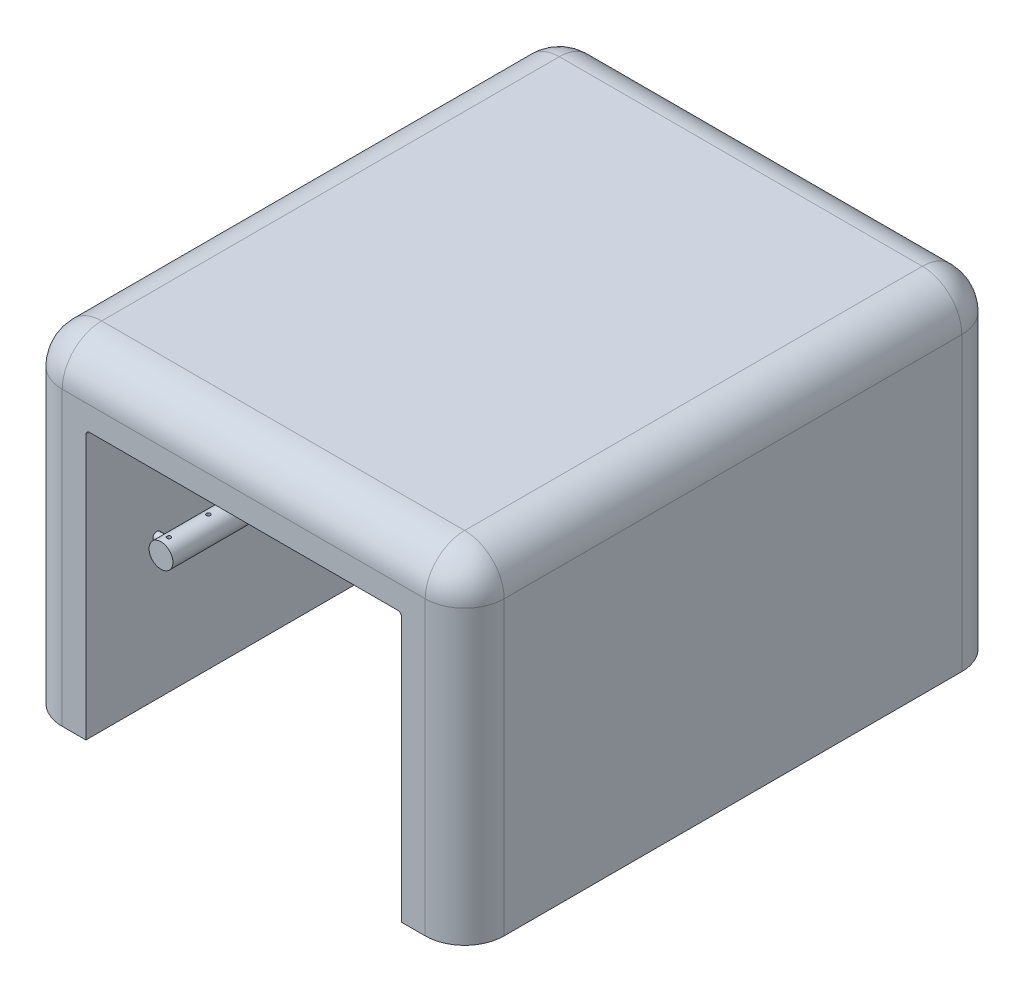
SolidWorks part; units mm, degrees
ref_plane "Front Plane" through (0, 0, 0) normal (0, 0, 1) x (1, 0, 0)
ref_plane "Top Plane" through (0, 0, 0) normal (0, 1, 0) x (1, 0, 0)
ref_plane "Right Plane" through (0, 0, 0) normal (1, 0, 0) x (0, 0, -1)
sketch "Sketch1" plane through (0, 0, 0) normal (1, 0, 0) x (0, 0, -1)
  line L1 (0, 0) -> (680, 0)
  line L2 (0, 0) -> (0, 420)
  line L3 (0, 420) -> (680, 420)
  line L4 (680, 0) -> (680, 420)
  dimension "D1" = 420
  dimension "D2" = 680
extrude "Boss-Extrude1" add sketch "Sketch1" along normal blind 560
sketch "Sketch4" plane through (0, 0, 0) normal (0, 0, 1) x (1, 0, 0)
  line L0 (560, 0) -> (0, 0) construction
  line L1 (80, 0) -> (480, 0)
  line L2 (80, 0) -> (80, 340)
  line L3 (80, 340) -> (480, 340)
  line L4 (480, 0) -> (480, 340)
  line L5 (560, 420) -> (560, 0) construction
  line L6 (560, 420) -> (0, 420) construction
  line L7 (0, 420) -> (0, 0) construction
  dimension "D1" = 80
  dimension "D2" = 80
  dimension "D3" = 80
extrude "Cut-Extrude1" cut sketch "Sketch4" against normal offset from surface (560 mm away) 120 up to face at (280, 210, -680)
ref_plane "Plane1" through (80, 0, 0) normal (1, 0, 0) x (0, 0, -1)
sketch "Sketch6" plane through (80, 0, 0) normal (1, 0, 0) x (0, 0, -1)
  line L1 (580, 80) -> (560, 80)
  line L2 (560, 80) -> (560, 160)
  line L3 (680, 0) -> (680, 420) construction
  line L4 (0, 0) -> (680, 0) construction
  line L5 (560, 160) -> (580, 160)
  line L6 (580, 160) -> (580, 80)
  dimension "D1" = 80
  dimension "D2" = 120
  dimension "D3" = 100
  dimension "D4" = 80
extrude "Cut-Extrude2" cut sketch "Sketch6" along normal up to surface (400 mm away) up to face at (480, 170, -280)
sketch "Sketch7" plane through (0, 0, -560) normal (0, 0, 1) x (1, 0, 0)
  line L3 (80, 160) -> (80, 340) construction
  line L5 (480, 160) -> (80, 160) construction
  circle A0 centre (105.125, 180.125) radius 15.125
  point P7 (280, 340)
  dimension "D1" = 30.25
  dimension "D2" = 5
  dimension "D3" = 10
extrude "Boss-Extrude2" add sketch "Sketch7" along normal offset from surface (490 mm away) 70 up to face at (280, 190, 0)
ref_plane "Plane2" through (0, 195.25, 0) normal (0, 1, 0) x (1, 0, 0)
ref_plane "Plane3" through (0, 0, -74) normal (0, 0, 1) x (1, 0, 0)
sketch "Sketch10" plane through (0, 0, -70) normal (0, 0, 1) x (1, 0, 0)
  circle A0 centre (105.125, 180.125) radius 11.125
  circle A1 centre (105.125, 180.125) radius 15.125 construction
  dimension "D1" = 4
extrude "Cut-Extrude3" cut sketch "Sketch10" against normal up to surface (490 mm away) from surface up to face at (120.25, 180.125, -560) starting at plane "Plane3"
sketch "Sketch9" plane through (0, 195.25, 0) normal (0, 1, 0) x (1, 0, 0)
  line L0 (90, 530) -> (120.25, 530) construction
  line L1 (90, 560) -> (90, 70) construction
  line L2 (120.25, 70) -> (120.25, 560) construction
  line L3 (80, 560) -> (480, 560) construction
  circle A0 centre (105.125, 530) radius 2.5
  circle A1 centre (105.125, 480) radius 2.5
  circle A2 centre (105.125, 430) radius 2.5
  circle A3 centre (105.125, 380) radius 2.5
  circle A4 centre (105.125, 330) radius 2.5
  circle A5 centre (105.125, 280) radius 2.5
  circle A6 centre (105.125, 230) radius 2.5
  circle A7 centre (105.125, 180) radius 2.5
  circle A8 centre (105.125, 130) radius 2.5
  circle A9 centre (105.125, 80) radius 2.5
  point P10 (105.125, 530)
  dimension "D1" = 5
  dimension "D2" = 30
  dimension "D3" = 10
extrude "Cut-Extrude4" cut sketch "Sketch9" against normal up to next
ref_axis "Axis1" through (280, 340, -560) along (0, -1, 0)
ref_plane "Plane4" through (280, 0, 0) normal (1, 0, 0) x (0, 0, -1)
sketch "Sketch11" plane through (80, 0, 0) normal (1, 0, 0) x (0, 0, -1)
  line L0 (70, 195.25) -> (70, 165) construction
  circle A0 centre (90, 179) radius 5
  dimension "D2" = 10
  dimension "D1" = 20
  dimension "D3" = 19
extrude "Boss-Extrude3" add sketch "Sketch11" along normal up to next
mirror "Mirror1" about plane through (280, 0, 0) normal (1, 0, 0) of "Boss-Extrude3", "Cut-Extrude3", "Cut-Extrude4", "Boss-Extrude2"
fillet "Fillet2" radius 50 8 edges at (280, 420, -680) (560, 420, -340) (280, 420, 0) (0, 420, -340) (0, 210, 0) (560, 210, 0) (560, 210, -680) (0, 210, -680)
fillet "Fillet3" radius 5 17 edges at (480, 40, -560) (80, 40, -560) (480, 80, -570) (80, 80, -570) (280, 80, -560) (480, 340, -280) (480, 250, -560) (280, 340, -560) (80, 250, -560) (80, 340, -280) (80, 160, -570) (280, 160, -560) (480, 160, -570) (280, 80, -580) (80, 120, -580) (280, 160, -580) (480, 120, -580)
